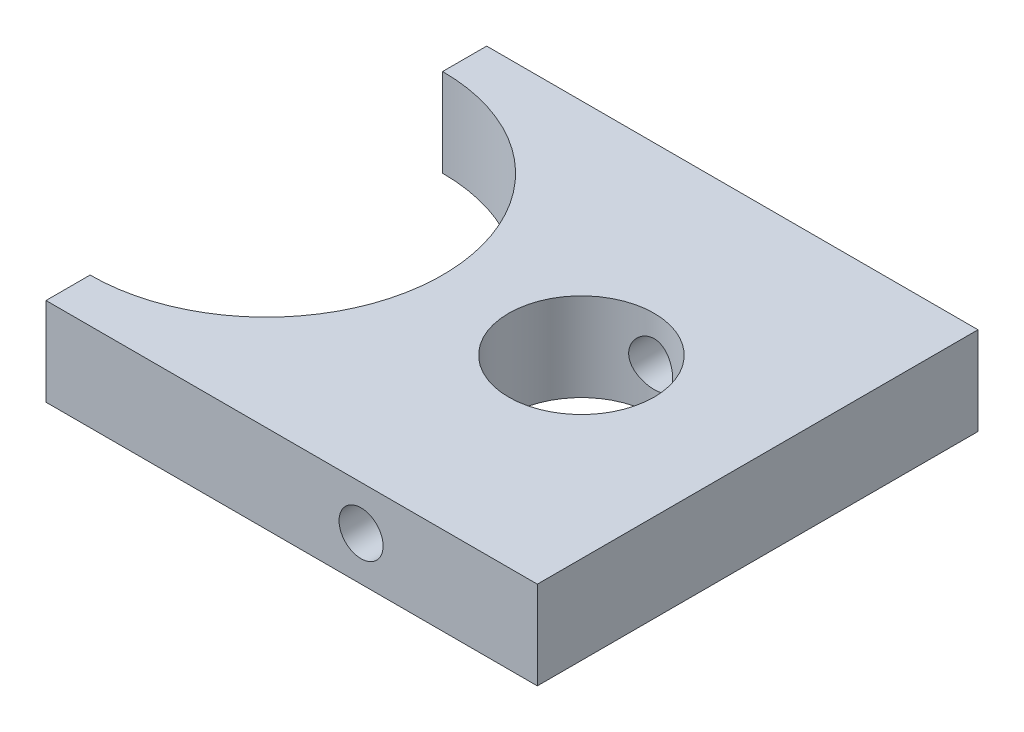
SolidWorks part; units mm, degrees
ref_plane "Front Plane" through (0, 0, 0) normal (0, 0, 1) x (1, 0, 0)
ref_plane "Top Plane" through (0, 0, 0) normal (0, 1, 0) x (1, 0, 0)
ref_plane "Right Plane" through (0, 0, 0) normal (1, 0, 0) x (0, 0, -1)
sketch "Sketch1" plane through (0, 0, 0) normal (0, 1, 0) x (1, 0, 0)
  line L0 (50.8, 127) -> (50.8, 0) construction
  line L1 (0, 0) -> (141.605, 0)
  line L2 (0, 0) -> (0, 12.7)
  line L3 (0, 127) -> (141.605, 127)
  line L5 (0, 114.3) -> (0, 127)
  line L6 (141.605, 0) -> (141.605, 127)
  line L7 (69.85, 63.5) -> (69.85, 0) construction
  arc A0 (0, 114.3) -> (0, 12.7) centre (0, 63.5) cw
  circle A1 centre (90.805, 63.5) radius 20.955
  point P7 (0, 114.3)
  point P8 (0, 12.7)
  dimension "D1" = 127
  dimension "D2" = 19.05
  dimension "D3" = 50.8
  dimension "D4" = 12.7
  dimension "D5" = 12.7
  dimension "D7" = 50.8
extrude "Boss-Extrude1" add sketch "Sketch1" along normal blind 25.4
sketch "Sketch2" plane through (0, 0, 0) normal (0, 0, 1) x (1, 0, 0)
  line L0 (141.605, 25.4) -> (141.605, 0) construction
  line L1 (0, 25.4) -> (141.605, 25.4) construction
  circle A0 centre (90.805, 12.7) radius 6.35
  dimension "D1" = 50.8
  dimension "D2" = 12.7
extrude "Cut-Extrude1" cut sketch "Sketch2" against normal through all
